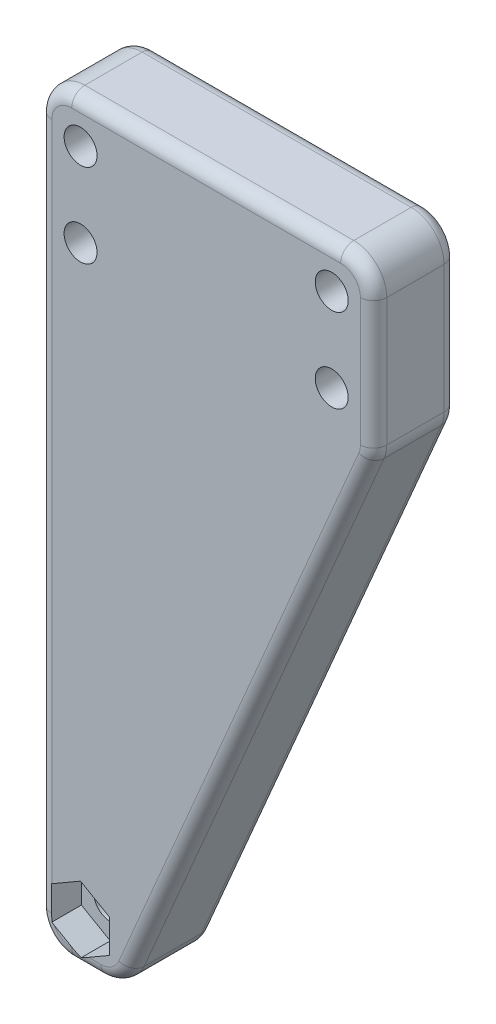
SolidWorks part; units mm, degrees
ref_plane "Front Plane" through (0, 0, 0) normal (0, 0, 1) x (1, 0, 0)
ref_plane "Top Plane" through (0, 0, 0) normal (0, 1, 0) x (1, 0, 0)
ref_plane "Right Plane" through (0, 0, 0) normal (1, 0, 0) x (0, 0, -1)
sketch "Sketch1" plane through (0, 0, 0) normal (0, 0, 1) x (1, 0, 0)
  line L0 (0, 0) -> (0, -114.3)
  line L1 (0, -114.3) -> (12.7, -114.3)
  line L2 (12.7, -114.3) -> (50.8, -25.4)
  line L3 (50.8, -25.4) -> (50.8, 0)
  line L4 (50.8, 0) -> (0, 0)
  circle A0 centre (6.35, -6.35) radius 2.5
  circle A1 centre (6.35, -107.95) radius 2.5
  circle A2 centre (44.45, -6.35) radius 2.5
  circle A3 centre (44.45, -19.05) radius 2.5
  circle A4 centre (6.35, -19.05) radius 2.5
  dimension "D7" = 5
  dimension "D1" = 114.3
  dimension "D2" = 50.8
  dimension "D3" = 25.4
  dimension "D4" = 12.7
  dimension "D5" = 6.35
  dimension "D6" = 6.35
  dimension "D8" = 6.35
  dimension "D9" = 2
  dimension "D10" = 2
extrude "Boss-Extrude1" add sketch "Sketch1" along normal blind 12.7
sketch "Sketch2" plane through (0, 0, 12.7) normal (0, 0, 1) x (1, 0, 0)
  line L1 (6.35, -113.0018) -> (10.725, -110.4759)
  line L2 (10.725, -110.4759) -> (10.725, -105.4241)
  line L3 (10.725, -105.4241) -> (6.35, -102.8982)
  line L4 (6.35, -102.8982) -> (1.975, -105.4241)
  line L5 (1.975, -105.4241) -> (1.975, -110.4759)
  line L6 (1.975, -110.4759) -> (6.35, -113.0018)
  circle A0 centre (6.35, -107.95) radius 4.375 construction
  point P0 (6.35, -107.95)
  dimension "D1" = 8.75
extrude "Cut-Extrude1" cut sketch "Sketch2" against normal blind 4.5
fillet "Fillet1" radius 5 5 edges at (0, -114.3, 6.35) (12.7, -114.3, 6.35) (50.8, -25.4, 6.35) (50.8, 0, 6.35) (0, 0, 6.35)
fillet "Fillet2" radius 2 20 edges at (50.6979, -25.379, 12.7) (32.1972, -68.8065, 12.7) (12.1555, -113.4742, 12.7) (7.2015, -114.3, 12.7) (1.4645, -112.8355, 12.7) (0, -57.15, 12.7) (1.4645, -1.4645, 12.7) (25.4, 0, 12.7) (49.3355, -1.4645, 12.7) (12.1555, -113.4742, 0) (7.2015, -114.3, 0) (1.4645, -112.8355, 0) (0, -57.15, 0) (1.4645, -1.4645, 0) (25.4, 0, 0) (49.3355, -1.4645, 0) (50.8, -14.6869, 0) (50.6979, -25.379, 0) (50.8, -14.6869, 12.7) (32.1972, -68.8065, 0)
